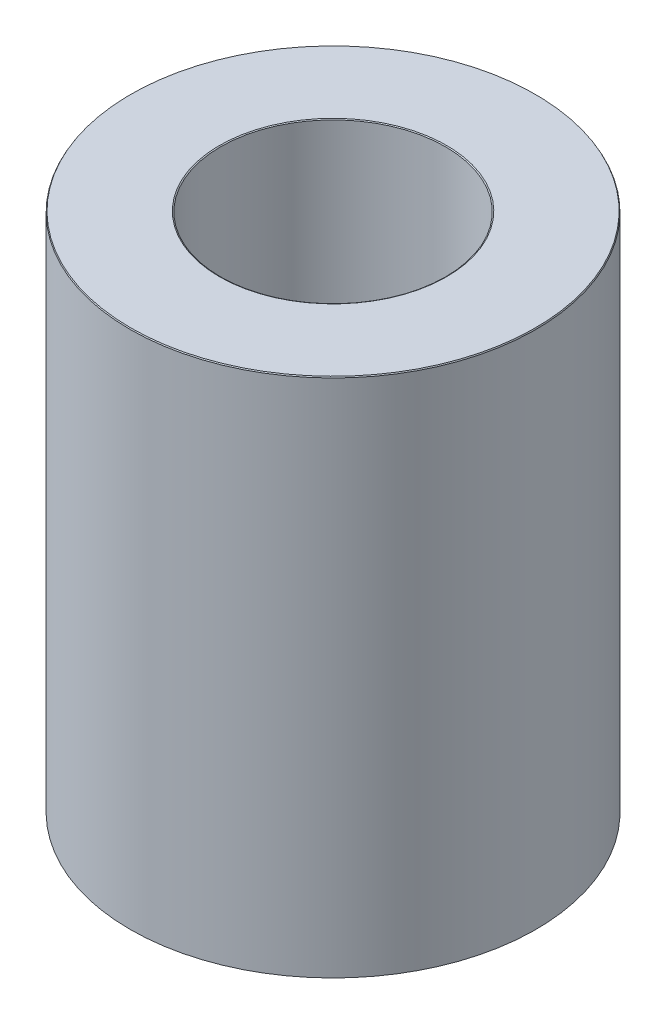
SolidWorks part; units mm, degrees
ref_plane "Front Plane" through (0, 0, 0) normal (0, 0, 1) x (1, 0, 0)
ref_plane "Top Plane" through (0, 0, 0) normal (0, 1, 0) x (1, 0, 0)
ref_plane "Right Plane" through (0, 0, 0) normal (1, 0, 0) x (0, 0, -1)
sketch "Sketch1" plane through (0, 0, 0) normal (0, 1, 0) x (1, 0, 0)
  circle A0 centre (0, 0) radius 45
  dimension "SLEEVE_OD" = 90
extrude "Boss-Extrude1" add sketch "Sketch1" along normal blind 115.612
sketch "Sketch2" plane through (0, 0, 0) normal (0, 1, 0) x (1, 0, 0)
  circle A0 centre (0, 0) radius 24.9727
  dimension "BORE_D" = 49.9455
extrude "Cut-Extrude1" cut sketch "Sketch2" along normal through all
chamfer "Chamfer1" distance 0.2358 angle 30 4 edges at (0, 115.612, 24.9727) (0, 0, 24.9727) (0, 0, 45) (0, 115.612, 45) first distance on face at (0, 115.612, 24.9727) first distance on face at (0, 0, 24.9727) first distance on face at (0, 115.612, 45)
